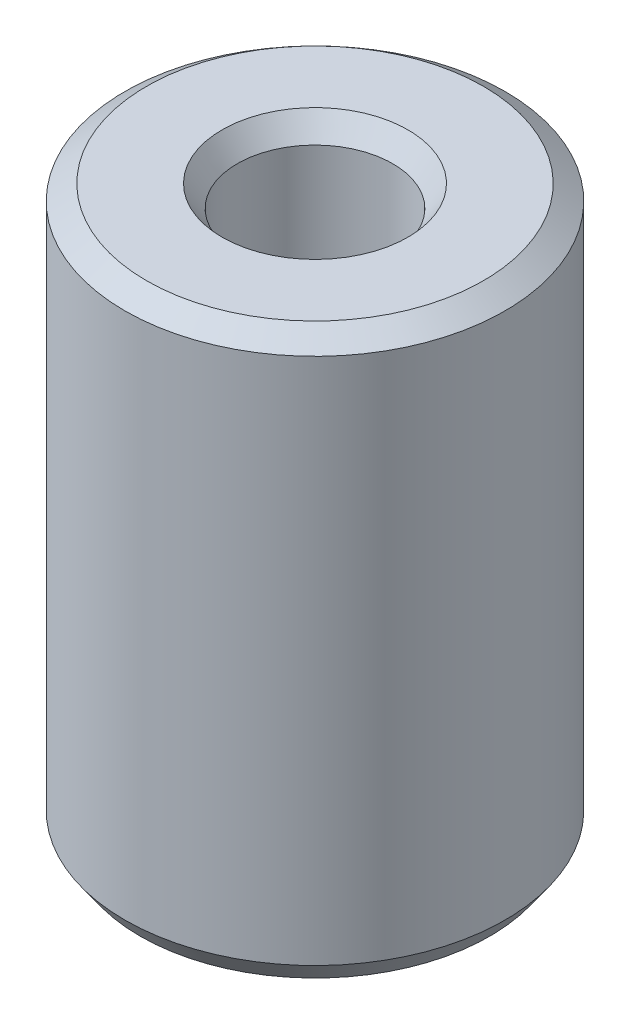
SolidWorks part; units mm, degrees
ref_plane "Front Plane" through (0, 0, 0) normal (0, 0, 1) x (1, 0, 0)
ref_plane "Top Plane" through (0, 0, 0) normal (0, 1, 0) x (1, 0, 0)
ref_plane "Right Plane" through (0, 0, 0) normal (1, 0, 0) x (0, 0, -1)
sketch "Sketch1" plane through (0, 0, 0) normal (0, 1, 0) x (1, 0, 0)
  circle A0 centre (0, 0) radius 15
  dimension "SLEEVE_OD" = 30
extrude "Boss-Extrude1" add sketch "Sketch1" along normal blind 44.5514
sketch "Sketch2" plane through (0, 0, 0) normal (0, 1, 0) x (1, 0, 0)
  circle A0 centre (0, 0) radius 6.1337
  dimension "BORE_D" = 12.2674
extrude "Cut-Extrude1" cut sketch "Sketch2" along normal through all
chamfer "Chamfer1" distance 1.2057 angle 54.773 4 edges at (0, 44.5514, 6.1337) (0, 0, 6.1337) (0, 0, 15) (0, 44.5514, 15) first distance on face at (0, 44.5514, 6.1337) first distance on face at (0, 0, 6.1337) first distance on face at (0, 44.5514, 15)
